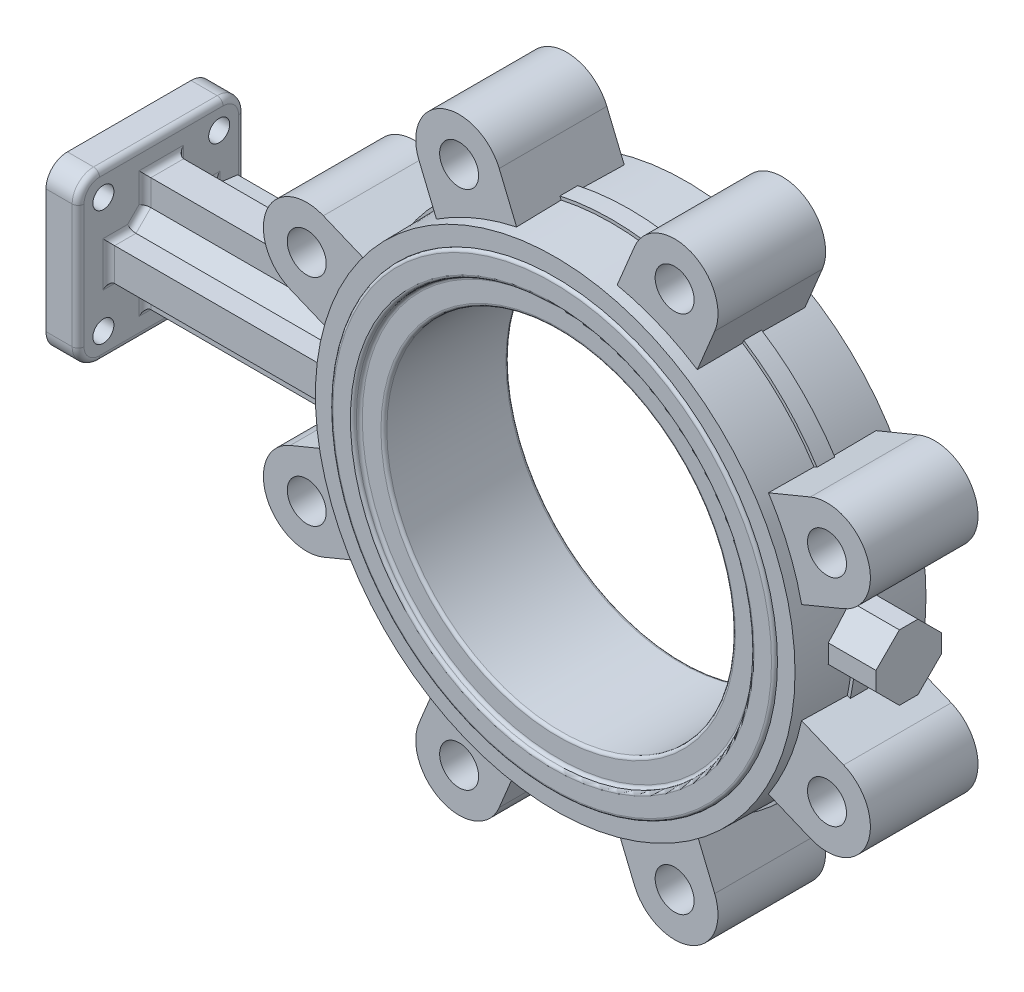
SolidWorks part; units mm, degrees
note: '?' marks a value the reader was unsure of.
material "A36"
ref_plane "Front Plane" through (0, 0, 0) normal (0, 0, 1) x (1, 0, 0)
ref_plane "Top Plane" through (0, 0, 0) normal (0, 1, 0) x (1, 0, 0)
ref_plane "Right Plane" through (0, 0, 0) normal (1, 0, 0) x (0, 0, -1)
sketch "Sketch1" plane through (0, 0, 0) normal (0, 0, 1) x (1, 0, 0)
  circle A0 centre (0, 0) radius 103
  dimension "D1" = 206.0001
extrude "Boss-Extrude1" add sketch "Sketch1" along normal mid plane 55.9816 draft 1
sketch "Sketch2" plane through (0, 0, 27.9908) normal (0, 0, 1) x (1, 0, 0)
  circle A0 centre (0, 0) radius 95
  dimension "D1" = 190
extrude "Boss-Extrude2" add sketch "Sketch2" along normal blind 1.27
sketch "Sketch3" plane through (0, 0, -27.9908) normal (0, 0, -1) x (-1, 0, 0)
  circle A0 centre (0, 0) radius 95
  circle A1 centre (0, 0) radius 95 construction
extrude "Boss-Extrude3" add sketch "Sketch3" along normal blind 1.27
sketch "Sketch5" plane through (0, 0, 29.2608) normal (0, 0, 1) x (1, 0, 0)
  circle A0 centre (0, 0) radius 85
  dimension "D1" = 170
extrude "Cut-Extrude2" cut sketch "Sketch5" against normal blind 2.54
sketch "Sketch4" plane through (0, 0, -29.2608) normal (0, 0, -1) x (-1, 0, 0)
  circle A0 centre (0, 0) radius 85
  circle A1 centre (0, 0) radius 85 construction
extrude "Cut-Extrude1" cut sketch "Sketch4" against normal blind 2.54
sketch "Sketch6" plane through (0, 0, 26.7208) normal (0, 0, 1) x (1, 0, 0)
  circle A0 centre (0, 0) radius 74.5
  dimension "D1" = 149
extrude "Cut-Extrude3" cut sketch "Sketch6" against normal through all both and the other way through all
sketch "Sketch7" plane through (0, 0, 0) normal (0, 1, 0) x (1, 0, 0)
  line L1 (-104.2895, 3.81) -> (-97.9395, 3.81)
  line L2 (-104.2895, 3.81) -> (-104.2895, -3.81)
  line L3 (-104.2895, -3.81) -> (-97.9395, -3.81)
  line L4 (-97.9395, 3.81) -> (-97.9395, -3.81)
  line L5 (-104.2895, 0) -> (-103, 0) construction
  line L7 (0, 0) -> (0, 27.9908) construction
  line L8 (102.5115, 27.9908) -> (-102.5115, 27.9908) construction
  dimension "D1" = 7.62
  dimension "D2" = 1.778
  dimension "D3" = 6.35
revolve "Revolve1" add sketch "Sketch7" angle 360 about L7
ref_plane "Plane1" through (104.2895, 0, 0) normal (1, 0, 0) x (0, 0, -1)
sketch "Sketch8" plane through (104.2895, 0, 0) normal (1, 0, 0) x (0, 0, -1)
  line L1 (-13.97, 13.97) -> (13.97, 13.97)
  line L2 (-13.97, 13.97) -> (-13.97, -13.97)
  line L3 (-13.97, -13.97) -> (13.97, -13.97)
  line L4 (13.97, 13.97) -> (13.97, -13.97)
  line L5 (-13.97, 13.97) -> (13.97, -13.97) construction
  line L6 (-13.97, -13.97) -> (13.97, 13.97) construction
  point P0 (0, 0)
  dimension "D1" = 27.94
extrude "Boss-Extrude4" add sketch "Sketch8" along normal blind 18.796 and the other way blind 10
chamfer "Chamfer1" distance 10 angle 45 4 edges at (112.4438, 13.97, -13.97) (112.4438, -13.97, -13.97) (112.4438, -13.97, 13.97) (112.4438, 13.97, 13.97)
ref_plane "Plane2" through (-104.2895, 0, 0) normal (-1, 0, 0) x (0, 0, 1)
sketch "Sketch9" plane through (-104.2895, 0, 0) normal (-1, 0, 0) x (0, 0, 1)
  line L1 (-22.479, 7) -> (-7, 7)
  line L2 (-22.479, 7) -> (-22.479, -7)
  line L3 (-22.479, -7) -> (-7, -7)
  line L4 (22.479, 7) -> (22.479, -7)
  line L5 (-22.479, 7) -> (22.479, -7) construction
  line L6 (-22.479, -7) -> (22.479, 7) construction
  line L7 (-7, -24.4094) -> (7, -24.4094)
  line L8 (-7, -24.4094) -> (-7, -7)
  line L9 (-7, 24.4094) -> (7, 24.4094)
  line L10 (7, -24.4094) -> (7, -7)
  line L11 (-7, -24.4094) -> (7, 24.4094) construction
  line L12 (-7, 24.4094) -> (7, -24.4094) construction
  line L13 (7, 7) -> (22.479, 7)
  line L14 (-7, 7) -> (-7, 24.4094)
  line L15 (7, 7) -> (7, 24.4094)
  line L19 (7, -7) -> (22.479, -7)
  point P0 (0, 0)
  point P5 (0, 0)
  dimension "D1" = 44.958
  dimension "D2" = 48.8188
  dimension "D3" = 14
extrude "Boss-Extrude5" add sketch "Sketch9" along normal blind 92.0664 and the other way blind 12.7
sketch "Sketch11" plane through (-196.3559, 0, 0) normal (-1, 0, 0) x (0, 0, 1)
  line L1 (35.56, 35.56) -> (-35.56, 35.56)
  line L2 (35.56, 35.56) -> (35.56, -35.56)
  line L3 (35.56, -35.56) -> (-35.56, -35.56)
  line L4 (-35.56, 35.56) -> (-35.56, -35.56)
  line L5 (35.56, 35.56) -> (-35.56, -35.56) construction
  line L6 (35.56, -35.56) -> (-35.56, 35.56) construction
  point P0 (0, 0)
  dimension "D1" = 71.12
extrude "Boss-Extrude7" add sketch "Sketch11" along normal blind 13.716
chamfer "Chamfer2" distance 6.35 angle 45 4 edges at (-149.4976, 7, 7) (-149.4976, -7, 7) (-149.4976, -7, -7) (-149.4976, 7, -7)
fillet "Fillet1" radius 9.144 4 edges at (-203.2139, 35.56, -35.56) (-203.2139, 35.56, 35.56) (-203.2139, -35.56, -35.56) (-203.2139, -35.56, 35.56)
sketch "Sketch12" plane through (0, 0, -3.81) normal (0, 0, -1) x (-1, 0, 0)
  line L0 (196.3559, 26.416) -> (196.3559, -26.416) construction
  line L1 (187.4659, 15.875) -> (130.3159, 15.875)
  line L2 (187.4659, 15.875) -> (187.4659, -15.875)
  line L3 (187.4659, -15.875) -> (130.3159, -15.875)
  line L4 (130.3159, 15.875) -> (130.3159, -15.875)
  line L5 (187.4659, 15.875) -> (130.3159, -15.875) construction
  line L6 (187.4659, -15.875) -> (130.3159, 15.875) construction
  line L7 (158.8909, 0) -> (0, 0) construction
  point P0 (158.8909, 0)
  dimension "D1" = 57.15
  dimension "D2" = 31.75
  dimension "D3" = 8.89
extrude "Boss-Extrude8" add sketch "Sketch12" along normal up to surface (18.669 mm away) draft 4
fillet "Fillet2" radius 1.27 8 edges at (85, 0, 26.7208) (74.5, 0, 26.7208) (-74.5, 0, -26.7208) (95, 0, 29.2608) (85, 0, 29.2608) (-95, 0, -29.2608) (-85, 0, -29.2608) (-85, 0, -26.7208)
sketch "Sketch14" plane through (-210.0719, 0, 0) normal (-1, 0, 0) x (0, 0, 1)
  circle A0 centre (0, 0) radius 11.5062
  dimension "D1" = 23.0124
extrude "Cut-Extrude5" cut sketch "Sketch14" against normal blind 7.62
hole_wizard "M8 Clearance Hole1" positions "Sketch16" profile "Sketch17" hole size "M8" standard "ANSI Metric"
sketch "Sketch16" plane through (-210.0719, 0, 0) normal (-1, 0, 0) x (0, 0, 1)
  line L1 (-24.7487, 24.7487) -> (24.7487, 24.7487)
  line L2 (-24.7487, 24.7487) -> (-24.7487, -24.7487)
  line L3 (-24.7487, -24.7487) -> (24.7487, -24.7487)
  line L4 (24.7487, 24.7487) -> (24.7487, -24.7487)
  line L5 (0, 0) -> (0, 24.7487)
  line L6 (0, 0) -> (0, -24.7487)
  point P0 (-24.7487, 24.7487)
  point P2 (24.7487, 24.7487)
  point P4 (24.7487, -24.7487)
  point P6 (-24.7487, -24.7487)
  dimension "D1" = 70
sketch "Sketch17" plane through (-210.0719, 24.7487, -24.7487) normal (0, 1, 0) x (0, 0, 1)
  line L0 (0, 0) -> (0, 13.716)
  line L1 (0, 13.716) -> (4.5, 13.716)
  line L2 (4.5, 13.716) -> (4.5, 0)
  line L5 (4.5, 0) -> (0, 0)
  line L11 (0, -6.35) -> (0, 107.95) construction
  dimension "Thru Hole Dia." = 9
  dimension "Thru Hole Depth" = 13.716
sketch "Sketch18" plane through (123.0855, 0, 0) normal (1, 0, 0) x (0, 0, -1)
  circle A0 centre (0, 0) radius 11.5
  dimension "D1" = 23
extrude "Boss-Extrude9" [suppressed] add sketch "Sketch18" against normal blind 211.328
sketch "Sketch19" plane through (-202.4519, 0, 0) normal (-1, 0, 0) x (0, 0, 1)
  circle A0 centre (0, 0) radius 9.0043
  dimension "D1" = 18.0086
extrude "Boss-Extrude10" [suppressed] add sketch "Sketch19" along normal offset from surface (6.62 mm away) 1
sketch "Sketch20" [suppressed] plane through (-209.0719, 0, 0) normal (-1, 0, 0) x (0, 0, 1)
  line L0 (0, 9.8783) -> (-9.8783, 0)
  line L5 (0, -9.8783) -> (9.8783, 0)
  line L6 (9.8783, 0) -> (0, 9.8783)
  line L7 (-9.8783, 0) -> (0, -9.8783)
  line L8 (-9.8783, 0) -> (9.8783, 0) construction
  line L9 (0, 9.8783) -> (0, -9.8783) construction
  point P4 (0, 0)
  dimension "D1" = 13.97
  dimension "D2" = 90
extrude "Boss-Extrude11" [suppressed] add sketch "Sketch20" along normal blind 19.5
chamfer "Chamfer3" [suppressed] distance 1.5 angle 45
sketch "Sketch21" plane through (0, 0, 0) normal (0, 0, 1) x (1, 0, 0)
  circle A2 centre (0, 0) radius 74
  dimension "D2" = 148
extrude "Boss-Extrude12" [suppressed] add sketch "Sketch21" along normal mid plane 3.33
sketch "Sketch22" plane through (0, 0, 0) normal (0, 0, 1) x (1, 0, 0)
  line L1 (0, 0) -> (-111.1845, 46.0541) construction
  line L2 (-74.1441, 0) -> (-210.0719, 0) construction
  line L4 (0, 0) -> (-48.4526, 0) construction
  line L5 (-210.0719, -26.416) -> (-210.0719, 26.416) construction
  line L7 (-104.0888, 63.1847) -> (-86.0504, 55.713)
  line L8 (-118.2802, 28.9235) -> (-100.2418, 21.4518)
  circle A4 centre (0, 0) radius 102.5115 construction
  arc A8 (-104.0888, 63.1847) -> (-118.2802, 28.9235) centre (-111.1845, 46.0541) ccw
  arc A9 (-86.0504, 55.713) -> (-100.2418, 21.4518) centre (0, 0) ccw
  dimension "D2" = 18.542
  dimension "D1" = 22.5
  dimension "D5" = 120.3452
extrude "Boss-Extrude13" add sketch "Sketch22" along normal mid plane 46
pattern_circular "CirPattern1" count 8 over 360 about axis through (0, 0, 0) along (0, 0, 1) of "Boss-Extrude13"
hole_wizard "3/4-10 Tapped Hole1" positions "Sketch23" profile "Sketch24" tap size "3/4-10" standard "ANSI Inch" end condition through all
sketch "Sketch23" plane through (0, 0, 23) normal (0, 0, 1) x (1, 0, 0)
  point P0 (-46.0541, 111.1845)
  point P3 (-111.1845, 46.0541)
  point P6 (111.1845, 46.0541)
  point P9 (46.0541, 111.1845)
  point P12 (111.1845, -46.0541)
  point P15 (46.0541, -111.1845)
  point P18 (-46.0541, -111.1845)
  point P21 (-111.1845, -46.0541)
  dimension "D1" = 120.3452
sketch "Sketch24" plane through (-46.0541, 111.1845, 23) normal (1, 0, 0) x (0, -1, 0)
  line L0 (0, 0) -> (0, 58.56)
  line L1 (0, 58.56) -> (8.3337, 58.56)
  line L2 (8.3337, 58.56) -> (8.3337, 0)
  line L5 (8.3337, 0) -> (0, 0)
  line L11 (0, -6.35) -> (0, 107.95) construction
  dimension "Thru Tap Drill Dia." = 16.6675
  dimension "Thru Tap Drill Depth" = 58.56
cosmetic thread "Hole Thread1" parameters "D2"=19.05
cosmetic thread "Hole Thread2" parameters "D2"=19.05
cosmetic thread "Hole Thread3" parameters "D2"=19.05
cosmetic thread "Hole Thread4" parameters "D2"=19.05
cosmetic thread "Hole Thread5" parameters "D2"=19.05
cosmetic thread "Hole Thread6" parameters "D2"=19.05
cosmetic thread "Hole Thread7" parameters "D2"=19.05
cosmetic thread "Hole Thread8" parameters "D2"=19.05
fillet "Fillet3" radius 2.54 24 edges at (-196.3559, -32.8818, 32.8818) (-196.3559, -35.56, 0) (-196.3559, -32.8818, -32.8818) (-196.3559, 0, -35.56) (-196.3559, 32.8818, -32.8818) (-196.3559, 35.56, 0) (-196.3559, 32.8818, 32.8818) (-196.3559, 7, 17.9145) (-196.3559, 24.4094, 0) (-196.3559, 10.175, -10.175) (-196.3559, 7, -17.9145) (-196.3559, 0, -22.479) (-196.3559, -7, -17.9145) (-196.3559, -10.175, -10.175) (-196.3559, -24.4094, 0) (-196.3559, -7, 17.9145) (-196.3559, 10.175, 10.175) (-196.3559, 0, 22.479) (-196.3559, -10.175, 10.175) (-196.3559, 0, 35.56) (-196.3559, -18.8797, -7) (-196.3559, -18.8797, 7) (-196.3559, 18.8797, 7) (-196.3559, 18.8797, -7)
ref_axis "Axis1" through (0, 0, -25.4508) along (0, 0, 1)?
ref_point "Point1"
ref_point "Point2"
ref_plane "Plane3" through (0, 0, 0) normal (1, 0, 0) x (0, 0, -1)
